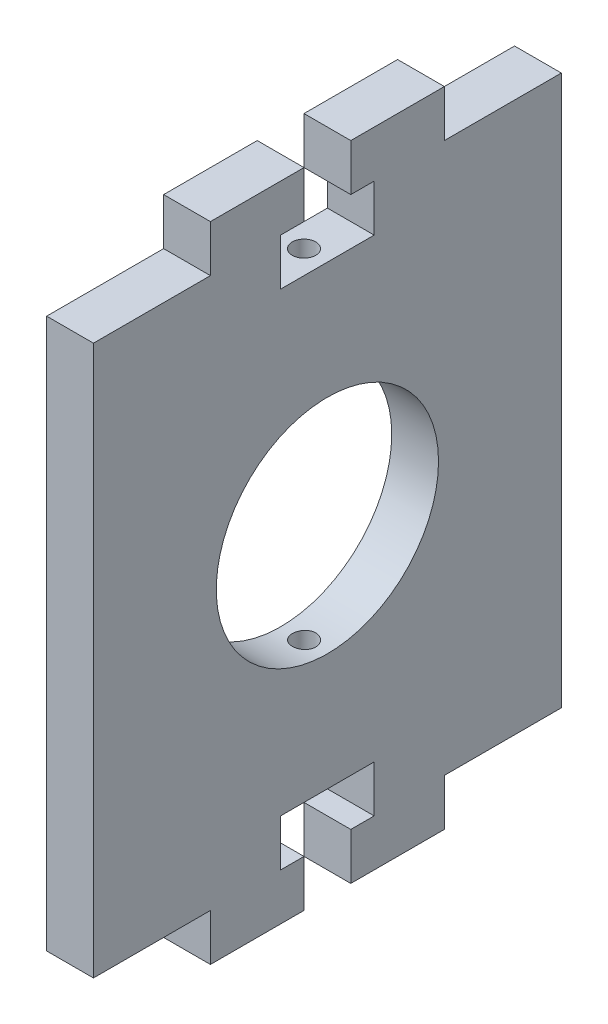
SolidWorks part; units mm, degrees
material "Ст 3 ГОСТ 380-88"
ref_plane "Спереди" through (0, 0, 0) normal (0, 0, 1) x (1, 0, 0)
ref_plane "Сверху" through (0, 0, 0) normal (0, 1, 0) x (1, 0, 0)
ref_plane "Справа" through (0, 0, 0) normal (1, 0, 0) x (0, 0, -1)
other "Configuration Table"
sketch "Эскиз1" plane through (0, 0, 0) normal (1, 0, 0) x (0, 0, -1)
  line L0 (30, -47) -> (40, -47)
  line L1 (0, 0) -> (10, 0)
  line L2 (0, 0) -> (0, -47)
  line L3 (0, -47) -> (10, -47)
  line L4 (40, 0) -> (40, -47)
  line L6 (10, -47) -> (10, -51)
  line L7 (10, -51) -> (18, -51)
  line L8 (30, -47) -> (30, -51)
  line L9 (22, -51) -> (30, -51)
  line L11 (18, -51) -> (18, -47)
  line L13 (22, -51) -> (22, -47)
  line L14 (16, -43) -> (24, -43)
  line L15 (16, -43) -> (16, -47)
  line L16 (16, -47) -> (18, -47)
  line L17 (24, -43) -> (24, -47)
  line L18 (22, -47) -> (24, -47)
  line L19 (30, 0) -> (40, 0)
  line L21 (10, 0) -> (10, 4)
  line L22 (10, 4) -> (18, 4)
  line L23 (30, 0) -> (30, 4)
  line L24 (22, 0) -> (24, 0)
  line L26 (18, 4) -> (18, 0)
  line L28 (22, 4) -> (22, 0)
  line L29 (16, 0) -> (18, 0)
  line L30 (16, 0) -> (16, -4)
  line L31 (16, -4) -> (24, -4)
  line L32 (24, 0) -> (24, -4)
  line L35 (22, 4) -> (30, 4)
  circle A0 centre (20, -23.5) radius 9.5
  circle A1 centre (20, -23.5) radius 17.5 construction
  dimension "D3" = 19
  dimension "D19" = 35
  dimension "D1" = 47
  dimension "D2" = 40
  dimension "D4" = 20
  dimension "D5" = 23.5
  dimension "D6" = 10
  dimension "D7" = 20
  dimension "D8" = 4
  dimension "D9" = 4
  dimension "D10" = 8
  dimension "D11" = 2
  dimension "D12" = 2
  dimension "D13" = 4
  dimension "D14" = 4
  dimension "D15" = 20
  dimension "D16" = 4
  dimension "D17" = 4
  dimension "D18" = 10
base flange "Базовая кромка1" sketch "Эскиз1" thickness 4 reverse thickness direction no parameters "D1"=0.7366
sketch "Эскиз6" plane through (0, 4, 0) normal (0, 1, 0) x (1, 0, 0)
  line L0 (-4, 22) -> (0, 22) construction
  line L1 (0, 18) -> (0, 10) construction
  circle A0 centre (-2, 20) radius 1
  dimension "D3" = 2
  dimension "D1" = 2
  dimension "D2" = 2
extrude "Вырез-Вытянуть1" cut sketch "Эскиз6" against normal through all normal cut yes
sketch "Сгиб-Линии1" [suppressed] plane through (0, 0, 0) normal (0, 1, 0) x (1, 0, 0)
sketch "Граничная рамка1" [suppressed] plane through (0, 0, 0) normal (0, 1, 0) x (1, 0, 0)
sheet metal parameters "Листовой металл3" thickness 4 parameters "D1"=0.7366
flat pattern "Развертка3" [suppressed]
sketch "Сгиб-Линии2" plane through (0, 0, 0) normal (0, 1, 0) x (1, 0, 0)
sketch "Граничная рамка2" [suppressed] plane through (0, 0, 0) normal (0, 1, 0) x (1, 0, 0)
sheet metal parameters "Листовой металл4" thickness 4 parameters "D1"=0.7366
flat pattern "Развертка3"
sketch "Сгиб-Линии2" plane through (0, 0, 0) normal (0, 1, 0) x (1, 0, 0)
sketch3d "Граничная рамка2" [suppressed]
  line L0 (40, 4, 0) -> (40, -51, 0) construction
  line L1 (0, 4, 0) -> (0, -51, 0) construction
  line L2 (40, 4, 0) -> (0, 4, 0) construction
  line L3 (40, -51, 0) -> (0, -51, 0) construction
